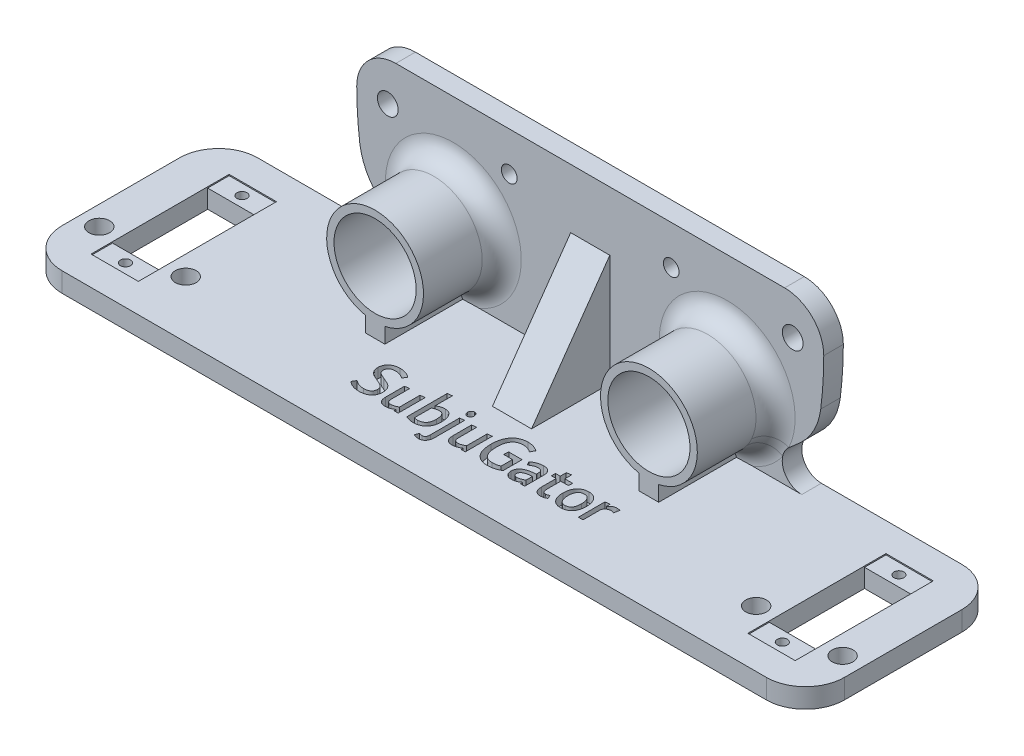
SolidWorks part; units mm, degrees
material "PET"
ref_plane "Front Plane" through (0, 0, 0) normal (0, 0, 1) x (1, 0, 0)
ref_plane "Top Plane" through (0, 0, 0) normal (0, 1, 0) x (1, 0, 0)
ref_plane "Right Plane" through (0, 0, 0) normal (1, 0, 0) x (0, 0, -1)
sketch "Sketch1" plane through (0, 0, 0) normal (0, 0, 1) x (1, 0, 0)
  line L0 (-63.1088, 12.7) -> (63.1088, 12.7)
  line L1 (0, 0) -> (0, 50000) construction
  circle A2 centre (-26.2895, 0) radius 2.5527
  circle A3 centre (-65.7237, 0) radius 3.3782
  arc A8 (-75.8088, 0) -> (-74.8207, -15.5281) centre (46.7003, 0) ccw
  arc A9 (-74.8207, -15.5281) -> (-68.3841, -28.0767) centre (-54.345, -12.9505) ccw
  arc A10 (-68.3841, -28.0767) -> (68.3841, -28.0767) centre (0, 46.0066) ccw
  arc A12 (-63.1088, 12.7) -> (-75.8088, 0) centre (-63.1088, 0) ccw
  circle A13 centre (26.2895, 0) radius 2.5527
  circle A14 centre (65.7237, 0) radius 3.3782
  arc A15 (74.8207, -15.5281) -> (68.3841, -28.0767) centre (54.345, -12.9505) cw
  arc A16 (75.8088, 0) -> (74.8207, -15.5281) centre (-46.7003, 0) cw
  arc A17 (63.1088, 12.7) -> (75.8088, 0) centre (63.1088, 0) cw
  point P11 (0, -54.8136)
  point P28 (0, 12.7)
  dimension "D1" = 65.7237
  dimension "D2" = 100.8202
  dimension "D3" = 5.1054
  dimension "D4" = 6.7564
  dimension "D5" = 12.7
  dimension "D7" = 20.6373
  dimension "D9" = 122.509
  dimension "D10" = 54.8136
  dimension "D6" = 12.7
  dimension "D8" = 26.2895
  dimension "D11" = 28.0767
  dimension "D12" = 15.5281
  dimension "D13" = 63.1088
extrude "Boss-Extrude1" add sketch "Sketch1" along normal blind 6.35
sketch "Sketch2" plane through (0, 0, 6.35) normal (0, 0, 1) x (1, 0, 0)
  line L0 (0, 0) -> (0, 50000) construction
  circle A0 centre (-44.45, -22.225) radius 13.335
  circle A1 centre (-44.45, -22.225) radius 8.89
  circle A2 centre (44.45, -22.225) radius 8.89
  circle A3 centre (44.45, -22.225) radius 13.335
  dimension "D1" = 26.67
  dimension "D4" = 17.78
  dimension "D2" = 44.45
  dimension "D3" = 22.225
extrude "Cut-Extrude2" cut sketch "Sketch2" against normal blind 3.175
sketch "Sketch3" plane through (0, 0, 6.35) normal (0, 0, 1) x (1, 0, 0)
  line L0 (0, 0) -> (0, 50000) construction
  circle A0 centre (44.45, -22.225) radius 15.7163
  circle A1 centre (44.45, -22.225) radius 13.335 construction
  circle A2 centre (44.45, -22.225) radius 13.335
  circle A3 centre (-44.45, -22.225) radius 13.335
  circle A4 centre (-44.45, -22.225) radius 15.7163
  dimension "D1" = 31.4325
extrude "Boss-Extrude2" add sketch "Sketch3" along normal blind 25.4
sketch "Sketch4" plane through (0, 0, 6.35) normal (0, 0, 1) x (1, 0, 0)
  line L4 (0, 0) -> (0, 50000) construction
  line L5 (-127, -42.6212) -> (127, -42.6212)
  line L6 (-127, -42.6212) -> (-127, -48.9712)
  line L7 (-127, -48.9712) -> (127, -48.9712)
  line L8 (127, -42.6212) -> (127, -48.9712)
  point P10 (0, -48.9712)
  point P11 (0, -42.6212)
  dimension "D1" = 6.35
  dimension "D2" = 127
  dimension "D3" = 42.6212
extrude "Boss-Extrude7" add sketch "Sketch4" along normal blind 57.15 and the other way blind 6.35
sketch "Sketch7" plane through (0, -42.6212, 0) normal (0, 1, 0) x (1, 0, 0)
  line L1 (-114.3, -16.2382) -> (-98.933, -16.2382)
  line L2 (-114.3, -16.2382) -> (-114.3, -47.15)
  line L3 (-114.3, -47.15) -> (-98.933, -47.15)
  line L4 (-98.933, -16.2382) -> (-98.933, -47.15)
  line L5 (0, 0) -> (0, 50000) construction
  line L6 (98.933, -16.2382) -> (98.933, -47.15)
  line L7 (114.3, -47.15) -> (98.933, -47.15)
  line L8 (114.3, -16.2382) -> (114.3, -47.15)
  line L9 (114.3, -16.2382) -> (98.933, -16.2382)
  line L10 (-114.3, -31.6941) -> (-98.933, -31.6941) construction
  line L11 (-106.6165, -16.2382) -> (-106.6165, 49983.7618) construction
  circle A0 centre (-106.6165, -50.612) radius 1.6256
  circle A1 centre (-106.6165, -12.7762) radius 1.6256
  circle A2 centre (106.6165, -12.7762) radius 1.6256
  circle A3 centre (106.6165, -50.612) radius 1.6256
  circle A4 centre (-120.65, -45.0799) radius 3.3782
  circle A5 centre (-92.583, -45.0799) radius 3.3782
  circle A6 centre (92.583, -45.0799) radius 3.3782
  circle A7 centre (120.65, -45.0799) radius 3.3782
  point P17 (-106.6165, -47.15)
  point P27 (-106.6165, -16.2382)
  dimension "D5" = 3.2512
  dimension "D9" = 6.7564
  dimension "D1" = 15.367
  dimension "D2" = 30.9118
  dimension "D3" = 114.3
  dimension "D4" = 3.462
  dimension "D6" = 16.2382
  dimension "D7" = 2.0701
  dimension "D8" = 6.35
extrude "Cut-Extrude3" cut sketch "Sketch7" against normal through all
sketch "Sketch8" plane through (0, -42.6212, 0) normal (0, 1, 0) x (1, 0, 0)
  line L0 (-114.3, -16.2382) -> (-114.3, -47.15) construction
  line L1 (-114.3, -9.2786) -> (-98.933, -9.2786)
  line L2 (-114.3, -9.2786) -> (-114.3, -54.1096)
  line L3 (-114.3, -54.1096) -> (-98.933, -54.1096)
  line L4 (-98.933, -9.2786) -> (-98.933, -54.1096)
  line L5 (-98.933, -47.15) -> (-98.933, -16.2382) construction
  line L6 (0, 0) -> (0, 50000) construction
  line L7 (63.1088, 0) -> (-63.1088, 0) construction
  line L8 (98.933, -9.2786) -> (98.933, -54.1096)
  line L9 (114.3, -54.1096) -> (98.933, -54.1096)
  line L10 (114.3, -9.2786) -> (114.3, -54.1096)
  line L11 (114.3, -9.2786) -> (98.933, -9.2786)
  point P7 (-114.3, -31.6941)
  point P8 (-114.3, -31.6941)
  point P15 (0, 0)
  dimension "D1" = 44.831
extrude "Cut-Extrude4" cut sketch "Sketch8" against normal blind 0.381
sketch "Sketch9" plane through (0, 0, 6.35) normal (0, 0, 1) x (1, 0, 0)
  line L0 (127, -42.6212) -> (-127, -42.6212) construction
  line L1 (-47.625, -36.2712) -> (-41.275, -36.2712)
  line L2 (-47.625, -36.2712) -> (-47.625, -42.6212)
  line L3 (-47.625, -42.6212) -> (-41.275, -42.6212)
  line L4 (-41.275, -36.2712) -> (-41.275, -42.6212)
  line L5 (0, 0) -> (0, 50000) construction
  line L6 (41.275, -36.2712) -> (41.275, -42.6212)
  line L7 (47.625, -42.6212) -> (41.275, -42.6212)
  line L8 (47.625, -36.2712) -> (47.625, -42.6212)
  line L9 (47.625, -36.2712) -> (41.275, -36.2712)
  circle A0 centre (-44.45, -22.225) radius 8.89 construction
  circle A1 centre (-44.45, -22.225) radius 8.89 construction
  point P17 (-44.45, -36.2712)
  dimension "D1" = 6.35
  dimension "D2" = 6.35
extrude "Boss-Extrude9" add sketch "Sketch9" along normal blind 25.4
sketch "Sketch10" plane through (0, 0, 0) normal (1, 0, 0) x (0, 0, -1)
  line L0 (-6.35, -42.6212) -> (-6.35, -6.5088)
  line L1 (-6.35, -6.5088) -> (-31.75, -42.6212)
  line L2 (-31.75, -42.6212) -> (-6.35, -42.6212)
extrude "Boss-Extrude10" add sketch "Sketch10" along normal mid plane 12.7
fillet "Fillet2" radius 6.35 3 edges at (0, -48.9712, 6.35) (-48.0606, -42.6212, 3.175) (48.0606, -42.6212, 3.175)
fillet "Fillet3" radius 6.35 2 edges at (44.45, -6.5088, 6.35) (-44.45, -6.5088, 6.35)
sketch "Sketch11" plane through (0, -42.6212, 0) normal (0, 1, 0) x (1, 0, 0)
  line L0 (-36.8413, -48.973) -> (39.3587, -48.973) construction
  text T0 "SubjuGator" font "Dubai" height 12.7
  point P3 (1.2587, -48.973)
  dimension "D1" = 76.2
  dimension "D2" = 50.8
extrude "Cut-Extrude6" cut sketch "Sketch11" against normal blind 3.175
fillet "Fillet4" radius 12.7 4 edges at (127, -45.7962, 0) (127, -45.7962, 63.5) (-127, -45.7962, 0) (-127, -45.7962, 63.5)
